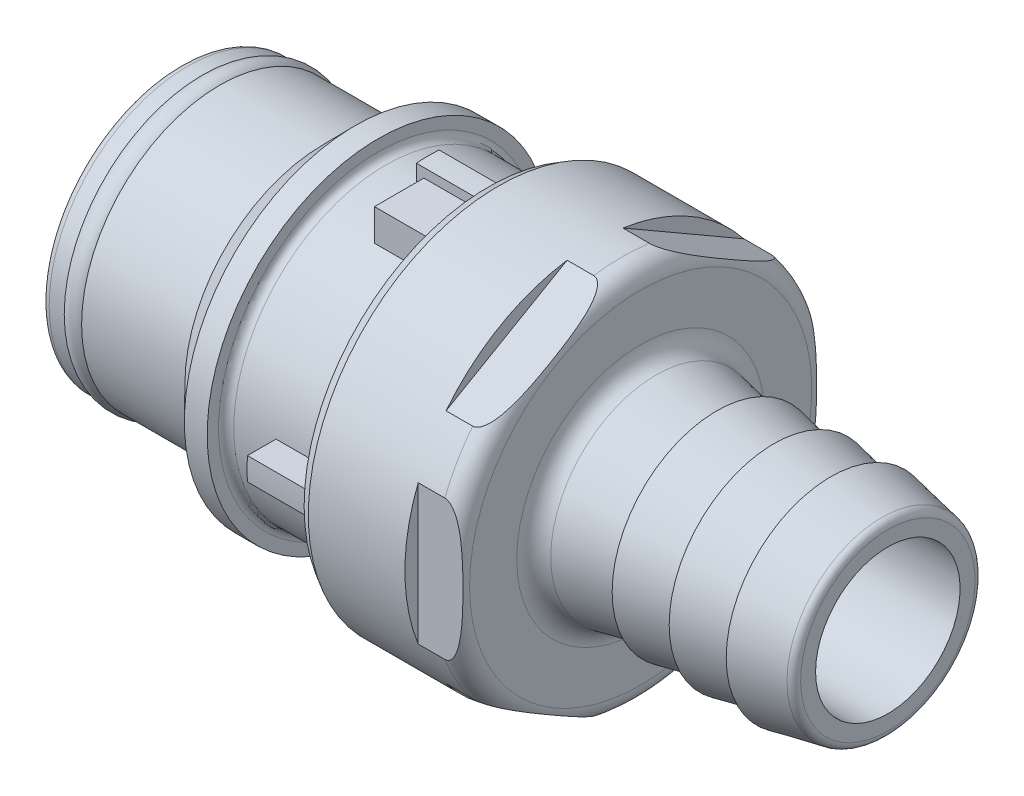
SolidWorks part; units mm, degrees
ref_plane "Front" through (0, 0, 0) normal (0, 0, 1) x (1, 0, 0)
ref_plane "Top" through (0, 0, 0) normal (0, 1, 0) x (1, 0, 0)
ref_plane "Right" through (0, 0, 0) normal (1, 0, 0) x (0, 0, -1)
ref_plane "Plane1" through (0, 0, 0) normal (0, 0, -1) x (-1, 0, 0)
sketch "Sketch1" plane through (0, 0, 0) normal (0, 0, -1) x (-1, 0, 0)
  line L0 (21.4503, 0) -> (19.6723, 0) construction
  arc A0 (19.6723, 8.7884) -> (21.4503, 8.7884) centre (20.5613, 9.0835) ccw
  arc A1 (21.4503, 8.7884) -> (19.6723, 8.7884) centre (20.5613, 8.5007) ccw
revolve "Revolve1" add sketch "Sketch1" angle 360 about L0 reverse direction yes
ref_plane "Plane2" through (0, 0, 0) normal (0, 0, -1) x (-1, 0, 0)
sketch "Sketch2" plane through (0, 0, 0) normal (0, 0, -1) x (-1, 0, 0)
  line L0 (0, 8.382) -> (9.558, 8.382)
  line L1 (9.558, 8.382) -> (9.558, 7.3614)
  line L2 (9.558, 7.3614) -> (11.7652, 7.3614)
  line L3 (11.7652, 7.3614) -> (12.2025, 6.604)
  line L4 (12.2025, 6.604) -> (22.6568, 6.604)
  line L5 (22.6568, 6.604) -> (22.6568, 8.7249)
  line L6 (22.1488, 9.2329) -> (13.081, 9.2329)
  line L7 (13.081, 9.2329) -> (10.922, 11.43)
  line L8 (10.922, 11.43) -> (9.398, 11.43)
  line L9 (9.398, 11.43) -> (9.398, 10.668)
  line L10 (8.89, 10.16) -> (3.302, 10.16)
  line L11 (2.032, 11.43) -> (2.032, 12.3187)
  line L12 (2.032, 12.3187) -> (1.3716, 12.7)
  line L13 (1.3716, 12.7) -> (0, 12.7)
  line L14 (0, 12.7) -> (0, 8.382)
  line L15 (22.6818, 0) -> (-22.225, 0) construction
  arc A0 (22.6568, 8.7249) -> (22.1488, 9.2329) centre (22.1488, 8.7249) ccw
  arc A1 (9.398, 10.668) -> (8.89, 10.16) centre (8.89, 10.668) cw
  arc A2 (3.302, 10.16) -> (2.032, 11.43) centre (3.302, 11.43) cw
revolve "Revolve2" add sketch "Sketch2" angle 360 about L15 reverse direction yes
ref_plane "Plane3" through (0, 0, 0) normal (0, 0, 1) x (1, 0, 0)
sketch "Sketch3" plane through (0, 0, 0) normal (0, 0, 1) x (1, 0, 0)
  line L0 (-25.4, 0) -> (-25.4, 2.159)
  line L1 (-25.4, 2.159) -> (-23.749, 2.159)
  line L2 (-21.717, 4.191) -> (-21.717, 4.572)
  line L3 (-21.336, 4.953) -> (-21.209, 4.953)
  line L4 (-21.209, 4.953) -> (-21.209, 3.8862)
  line L5 (-20.701, 3.3782) -> (-18.923, 3.3782)
  line L6 (-18.415, 3.8862) -> (-18.415, 5.6896)
  line L7 (-18.415, 5.6896) -> (-16.7132, 7.3914)
  line L8 (-16.7132, 7.3914) -> (-10.668, 7.3914)
  line L9 (-10.668, 7.3914) -> (-9.906, 8.1534)
  line L10 (-9.906, 8.1534) -> (0.254, 8.1534)
  line L11 (0.254, 8.1534) -> (0.254, 7.747)
  line L12 (0.254, 7.747) -> (-0.508, 6.985)
  line L13 (-0.508, 6.985) -> (-9.1443, 6.985)
  line L14 (-9.1443, 6.985) -> (-9.144, 5.715)
  line L15 (-9.144, 5.715) -> (-12.446, 5.715)
  line L16 (-12.446, 5.715) -> (-14.6002, 4.2066)
  line L17 (-14.2004, 1.9396) -> (-9.7088, 0.736)
  line L18 (-9.144, 0) -> (-25.4, 0)
  line L19 (-9.144, 0) -> (-25.4, 0) construction
  arc A0 (-23.749, 2.159) -> (-21.717, 4.191) centre (-23.749, 4.191) ccw
  arc A1 (-21.717, 4.572) -> (-21.336, 4.953) centre (-21.336, 4.572) cw
  arc A2 (-21.209, 3.8862) -> (-20.701, 3.3782) centre (-20.701, 3.8862) ccw
  arc A3 (-18.923, 3.3782) -> (-18.415, 3.8862) centre (-18.923, 3.8862) ccw
  arc A4 (-14.6002, 4.2066) -> (-14.2004, 1.9396) centre (-13.8717, 3.1663) ccw
  arc A5 (-9.7088, 0.736) -> (-9.144, 0) centre (-9.906, 0) cw
revolve "Revolve3" add sketch "Sketch3" angle 360 about L19 reverse direction yes
ref_plane "Plane4" through (-2.032, 0, 0) normal (-1, 0, 0) x (0, 0, 1)
sketch "Sketch4" plane through (-2.032, 0, 0) normal (-1, 0, 0) x (0, 0, 1)
  line L0 (-0.762, -10.1314) -> (-0.762, -12.0409)
  line L1 (0.762, -12.0409) -> (0.762, -10.1314)
  arc A0 (-0.762, -12.0409) -> (0.762, -12.0409) centre (0, 0) ccw
  arc A1 (0.762, -10.1314) -> (-0.762, -10.1314) centre (0, 0) cw
extrude "Boss-Extrude1" add sketch "Sketch4" along normal blind 4.064
ref_plane "Plane5" through (-2.032, 0, 0) normal (-1, 0, 0) x (0, 0, 1)
sketch "Sketch5" plane through (-2.032, 0, 0) normal (-1, 0, 0) x (0, 0, 1)
  line L0 (-12.0409, -0.762) -> (-10.1314, -0.762)
  line L1 (-10.1314, 0.762) -> (-12.0409, 0.762)
  arc A0 (-12.0409, 0.762) -> (-12.0409, -0.762) centre (0, 0) ccw
  arc A1 (-10.1314, -0.762) -> (-10.1314, 0.762) centre (0, 0) cw
extrude "Boss-Extrude2" add sketch "Sketch5" along normal blind 4.064
ref_plane "Plane6" through (-2.032, 0, 0) normal (-1, 0, 0) x (0, 0, 1)
sketch "Sketch6" plane through (-2.032, 0, 0) normal (-1, 0, 0) x (0, 0, 1)
  line L0 (4.064, 9.3118) -> (4.064, 11.43)
  line L1 (4.064, 11.43) -> (0.762, 11.43)
  line L2 (0.762, 11.43) -> (0.762, 12.0409)
  line L3 (-0.762, 12.0409) -> (-0.762, 10.1314)
  arc A0 (-0.762, 10.1314) -> (4.064, 9.3118) centre (0, 0) cw
  arc A1 (0.762, 12.0409) -> (-0.762, 12.0409) centre (0, 0) ccw
extrude "Boss-Extrude3" add sketch "Sketch6" along normal blind 3.556
ref_plane "Plane7" through (-2.032, 0, 0) normal (-1, 0, 0) x (0, 0, 1)
sketch "Sketch7" plane through (-2.032, 0, 0) normal (-1, 0, 0) x (0, 0, 1)
  line L0 (0.762, 10.1314) -> (0.762, 12.0409)
  line L1 (-0.762, 12.0409) -> (-0.762, 10.1314)
  arc A0 (-0.762, 10.1314) -> (0.762, 10.1314) centre (0, 0) cw
  arc A1 (0.762, 12.0409) -> (-0.762, 12.0409) centre (0, 0) ccw
extrude "Boss-Extrude4" add sketch "Sketch7" along normal blind 4.064
ref_plane "Plane8" through (-2.032, 0, 0) normal (-1, 0, 0) x (0, 0, 1)
sketch "Sketch8" plane through (-2.032, 0, 0) normal (-1, 0, 0) x (0, 0, 1)
  line L0 (10.1314, -0.762) -> (12.0409, -0.762)
  line L1 (12.0409, 0.762) -> (10.1314, 0.762)
  arc A0 (12.0409, -0.762) -> (12.0409, 0.762) centre (0, 0) ccw
  arc A1 (10.1314, 0.762) -> (10.1314, -0.762) centre (0, 0) cw
extrude "Boss-Extrude5" add sketch "Sketch8" along normal blind 4.064
ref_plane "Plane9" through (0, 0, 0) normal (0, -1, 0) x (1, 0, 0)
sketch "Sketch9" plane through (0, 0, 0) normal (0, -1, 0) x (1, 0, 0)
  line L0 (5.715, 4.826) -> (24.638, 4.826)
  line L1 (24.638, 4.826) -> (24.638, 5.8246)
  line L2 (24.2271, 6.3233) -> (20.828, 6.985)
  line L3 (20.828, 6.985) -> (20.828, 6.7056)
  line L4 (20.3742, 6.3316) -> (17.018, 6.985)
  line L5 (17.018, 6.985) -> (17.018, 6.7056)
  line L6 (16.5642, 6.3316) -> (13.208, 6.985)
  line L7 (13.208, 6.985) -> (13.208, 6.7056)
  line L8 (12.7542, 6.3316) -> (9.1553, 7.0322)
  line L9 (8.128, 8.2788) -> (8.128, 11.43)
  line L10 (6.858, 12.7) -> (0, 12.7)
  line L11 (0, 12.7) -> (0, 8.382)
  line L12 (0, 8.382) -> (3.302, 8.382)
  line L13 (3.302, 8.382) -> (3.302, 7.5565)
  line L14 (3.683, 7.1755) -> (5.207, 7.1755)
  line L15 (5.715, 6.6675) -> (5.715, 4.826)
  line L16 (24.663, 0) -> (0, 0) construction
  arc A0 (24.638, 5.8246) -> (24.2271, 6.3233) centre (24.13, 5.8246) ccw
  arc A1 (20.828, 6.7056) -> (20.3742, 6.3316) centre (20.447, 6.7056) cw
  arc A2 (17.018, 6.7056) -> (16.5642, 6.3316) centre (16.637, 6.7056) cw
  arc A3 (13.208, 6.7056) -> (12.7542, 6.3316) centre (12.827, 6.7056) cw
  arc A4 (9.1553, 7.0322) -> (8.128, 8.2788) centre (9.398, 8.2788) cw
  arc A5 (8.128, 11.43) -> (6.858, 12.7) centre (6.858, 11.43) ccw
  arc A6 (3.302, 7.5565) -> (3.683, 7.1755) centre (3.683, 7.5565) ccw
  arc A7 (5.207, 7.1755) -> (5.715, 6.6675) centre (5.207, 6.6675) cw
revolve "Revolve4" add sketch "Sketch9" angle 360 about L16 reverse direction yes
ref_plane "Plane10" through (5.08, 0, 0) normal (1, 0, 0) x (0, 0, -1)
sketch "Sketch10" plane through (5.08, 0, 0) normal (1, 0, 0) x (0, 0, -1)
  line L0 (-24.9961, 26.2247) -> (-24.9961, -28.0202)
  line L1 (-24.9961, -28.0202) -> (26.4137, -28.0202)
  line L2 (26.4137, -28.0202) -> (26.4137, 26.2247)
  line L3 (26.4137, 26.2247) -> (-24.9961, 26.2247)
  line L4 (-11.811, 6.8191) -> (-11.811, -6.8191)
  line L5 (-11.811, -6.8191) -> (0, -13.6382)
  line L6 (0, -13.6382) -> (11.811, -6.8191)
  line L7 (11.811, -6.8191) -> (11.811, 6.8191)
  line L8 (11.811, 6.8191) -> (0, 13.6382)
  line L9 (0, 13.6382) -> (-11.811, 6.8191)
extrude "Cut-Extrude1" cut sketch "Sketch10" along normal blind 10
